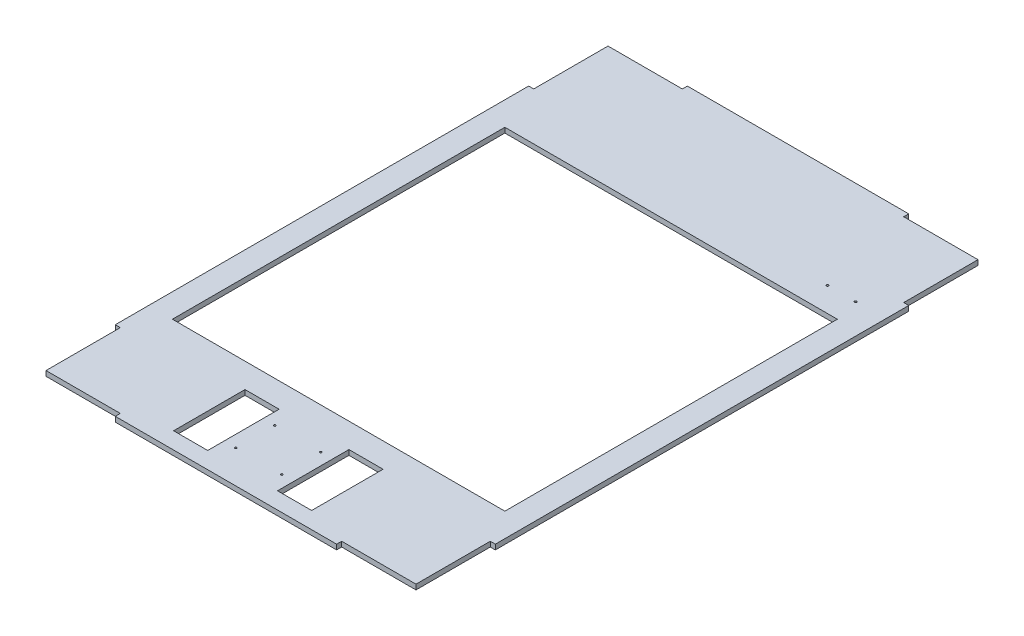
SolidWorks part; units mm, degrees
ref_plane "Front Plane" through (0, 0, 0) normal (0, 0, 1) x (1, 0, 0)
ref_plane "Top Plane" through (0, 0, 0) normal (0, 1, 0) x (1, 0, 0)
ref_plane "Right Plane" through (0, 0, 0) normal (1, 0, 0) x (0, 0, -1)
sketch "Sketch1" plane through (0, 0, 0) normal (0, 1, 0) x (1, 0, 0)
  line L0 (44, -285.5) -> (-44, -285.5) construction
  line L1 (-209.5, -209.5) -> (209.5, -209.5)
  line L2 (-209.5, -209.5) -> (-209.5, 209.5)
  line L3 (-209.5, 209.5) -> (209.5, 209.5)
  line L4 (209.5, -209.5) -> (209.5, 209.5)
  line L5 (-209.5, -209.5) -> (209.5, 209.5) construction
  line L6 (-209.5, 209.5) -> (209.5, -209.5) construction
  line L7 (-239.5, -351.5) -> (239.5, -351.5)
  line L8 (-239.5, -351.5) -> (-239.5, 369.5)
  line L9 (-239.5, 369.5) -> (239.5, 369.5)
  line L10 (239.5, -351.5) -> (239.5, 369.5)
  line L11 (-97, -340.5) -> (97, -340.5) construction
  line L12 (-97, -340.5) -> (-97, -230.5) construction
  line L13 (-97, -230.5) -> (97, -230.5) construction
  line L14 (97, -340.5) -> (97, -230.5) construction
  line L15 (-97, -340.5) -> (97, -230.5) construction
  line L16 (-97, -230.5) -> (97, -340.5) construction
  line L21 (29, -310) -> (-29, -310) construction
  line L22 (29, -310) -> (29, -261) construction
  line L23 (29, -261) -> (-29, -261) construction
  line L24 (-29, -310) -> (-29, -261) construction
  line L25 (29, -310) -> (-29, -261) construction
  line L26 (29, -261) -> (-29, -310) construction
  line L27 (-44, -330.5) -> (-87, -330.5)
  line L28 (-44, -330.5) -> (-44, -240.5)
  line L29 (-44, -240.5) -> (-87, -240.5)
  line L30 (-87, -330.5) -> (-87, -240.5)
  line L31 (87, -330.5) -> (44, -330.5)
  line L32 (87, -330.5) -> (87, -240.5)
  line L33 (87, -240.5) -> (44, -240.5)
  line L34 (44, -330.5) -> (44, -240.5)
  circle A0 centre (-29, -310) radius 1.25
  circle A1 centre (-29, -261) radius 1.25
  circle A2 centre (29, -261) radius 1.25
  circle A3 centre (29, -310) radius 1.25
  point P0 (0, 0)
  point P6 (0, 0)
  point P11 (0, -351.5)
  point P12 (0, -285.5)
  point P17 (0, -285.5)
  point P18 (0, -285.5)
  dimension "D10" = 2.5
  dimension "D1" = 419
  dimension "D2" = 30
  dimension "D3" = 11
  dimension "D4" = 160
  dimension "D5" = 194
  dimension "D6" = 110
  dimension "D7" = 21
  dimension "D8" = 58
  dimension "D9" = 49
  dimension "D11" = 10
  dimension "D12" = 15
  dimension "D13" = 10
extrude "Boss-Extrude1" add sketch "Sketch1" along normal mid plane 6.35
sketch "Sketch2" plane through (0, 3.175, 0) normal (0, 1, 0) x (1, 0, 0)
  line L0 (-239.5, 369.5) -> (-239.5, 269.5)
  line L1 (-239.5, 369.5) -> (-239.5, -351.5) construction
  line L2 (-239.5, 269.5) -> (-233.15, 269.5)
  line L3 (-233.15, 269.5) -> (-233.15, 363.15)
  line L4 (-233.15, 363.15) -> (-139.5, 363.15)
  line L5 (-139.5, 363.15) -> (-139.5, 369.5)
  line L6 (239.5, 369.5) -> (-239.5, 369.5) construction
  line L7 (-139.5, 369.5) -> (-239.5, 369.5)
  line L8 (239.5, 369.5) -> (139.5, 369.5)
  line L9 (139.5, 369.5) -> (139.5, 363.15)
  line L10 (139.5, 363.15) -> (233.15, 363.15)
  line L11 (233.15, 363.15) -> (233.15, 269.5)
  line L12 (233.15, 269.5) -> (239.5, 269.5)
  line L13 (239.5, -351.5) -> (239.5, 369.5) construction
  line L14 (239.5, 269.5) -> (239.5, 369.5)
  line L15 (239.5, -351.5) -> (239.5, -251.5)
  line L16 (239.5, -251.5) -> (233.15, -251.5)
  line L17 (233.15, -251.5) -> (233.15, -345.15)
  line L18 (233.15, -345.15) -> (139.5, -345.15)
  line L19 (139.5, -345.15) -> (139.5, -351.5)
  line L20 (-239.5, -351.5) -> (239.5, -351.5) construction
  line L21 (139.5, -351.5) -> (239.5, -351.5)
  line L22 (-239.5, -351.5) -> (-139.5, -351.5)
  line L23 (-139.5, -351.5) -> (-139.5, -345.15)
  line L24 (-139.5, -345.15) -> (-233.15, -345.15)
  line L25 (-233.15, -345.15) -> (-233.15, -251.5)
  line L26 (-233.15, -251.5) -> (-239.5, -251.5)
  line L27 (-239.5, -251.5) -> (-239.5, -351.5)
  dimension "D1" = 100
  dimension "D2" = 6.35
extrude "Cut-Extrude1" cut sketch "Sketch2" against normal through all
sketch "Sketch3" plane through (0, 3.175, 0) normal (0, 1, 0) x (1, 0, 0)
  line L0 (201.88, 240.12) -> (166.32, 240.12) construction
  line L2 (209.5, 209.5) -> (-209.5, 209.5) construction
  line L3 (161.24, 232.5) -> (209.5, 232.5) construction
  line L4 (161.24, 232.5) -> (161.24, 268.06) construction
  line L5 (161.24, 268.06) -> (209.5, 268.06) construction
  line L6 (209.5, 232.5) -> (209.5, 268.06) construction
  line L7 (209.5, -209.5) -> (209.5, 209.5) construction
  circle A0 centre (166.32, 240.12) radius 1.375
  circle A1 centre (201.88, 240.12) radius 1.375
  dimension "D2" = 2.75
  dimension "D1" = 35.56
  dimension "D3" = 35.56
  dimension "D4" = 48.26
  dimension "D5" = 40.64
  dimension "D6" = 27.94
  dimension "D7" = 23
extrude "Cut-Extrude2" cut sketch "Sketch3" against normal through all
